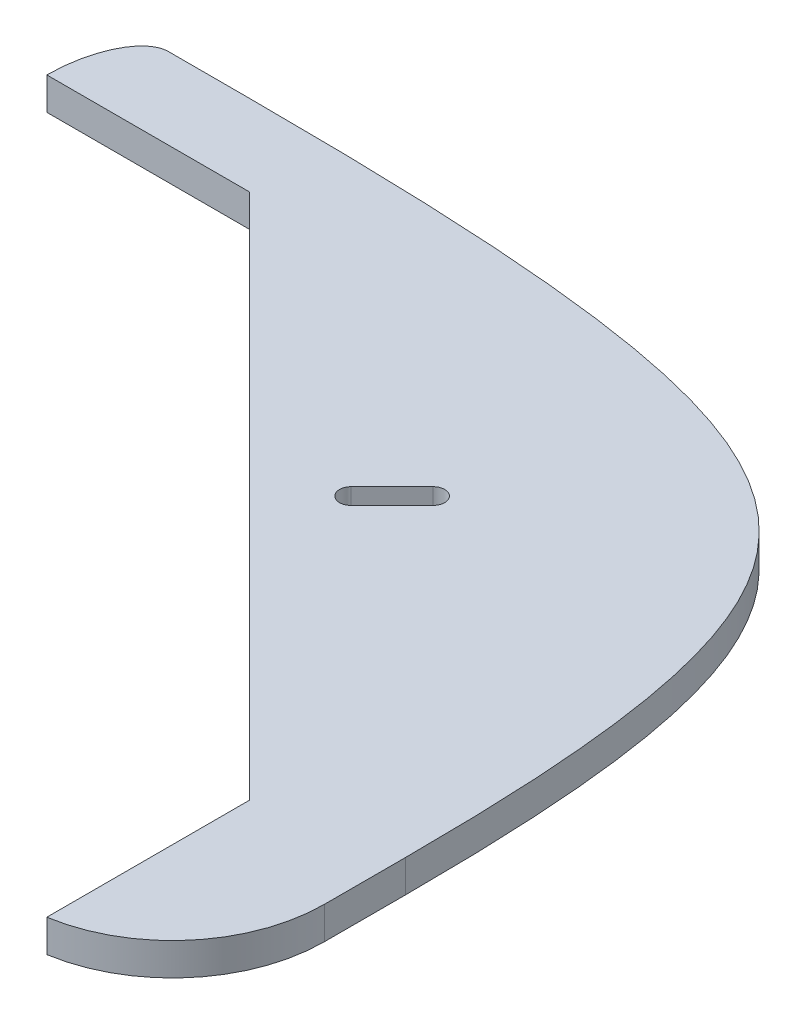
SolidWorks part; units mm, degrees
ref_plane "Front Plane" through (0, 0, 0) normal (0, 0, 1) x (1, 0, 0)
ref_plane "Top Plane" through (0, 0, 0) normal (0, 1, 0) x (1, 0, 0)
ref_plane "Right Plane" through (0, 0, 0) normal (1, 0, 0) x (0, 0, -1)
sketch "Sketch1" plane through (0, 0, 0) normal (0, 1, 0) x (1, 0, 0)
  line L1 (0, 120.65) -> (12.7, 120.65)
  line L3 (120.65, 0) -> (120.65, 12.7)
  line L4 (0, 107.95) -> (25.4, 107.95)
  line L5 (25.4, 107.95) -> (107.95, 25.4)
  line L6 (107.95, 25.4) -> (107.95, 0)
  line L7 (0, 0) -> (0, 107.95) construction
  line L8 (0, 107.95) -> (0, 120.65)
  line L9 (0, 0) -> (107.95, 0) construction
  line L10 (107.95, 0) -> (120.65, 0)
  line L12 (74.6363, 74.6363) -> (66.675, 66.675) construction
  line L13 (74.6363, 74.6363) -> (81.0709, 81.0709) construction
  line L14 (73.3635, 75.909) -> (79.7981, 82.3437)
  line L15 (75.909, 73.3635) -> (82.3437, 79.7981)
  line L16 (81.0709, 81.0709) -> (89.0322, 89.0322) construction
  arc A0 (12.7, 120.65) -> (120.65, 12.7) centre (12.7, 12.7) cw
  arc A1 (73.3635, 75.909) -> (75.909, 73.3635) centre (74.6363, 74.6363) ccw
  arc A2 (82.3437, 79.7981) -> (79.7981, 82.3437) centre (81.0709, 81.0709) ccw
  point P15 (77.8536, 77.8536)
  point P20 (73.3635, 73.3635)
  point P21 (82.3437, 82.3437)
  point P23 (79.1264, 76.5808)
  dimension "D5" = 12.7
  dimension "D1" = 25.4
  dimension "D2" = 120.65
  dimension "D3" = 12.7
  dimension "D4" = 12.7
  dimension "D6" = 3.6
extrude "Boss-Extrude1" add sketch "Sketch1" along normal blind 5.08
sketch "Sketch2" plane through (0, 0, 0) normal (-1, 0, 0) x (0, 0, 1)
  line L4 (-120.65, 0) -> (-107.95, 0)
  line L5 (-107.95, 0) -> (-107.95, 5.08)
  line L6 (-107.95, 5.08) -> (-120.65, 5.08)
  line L7 (-120.65, 5.08) -> (-120.65, 0)
  line L8 (-120.65, 0) -> (-107.95, 0)
  line L9 (-107.95, 0) -> (-107.95, 5.08)
  line L10 (-107.95, 5.08) -> (-120.65, 5.08)
  line L11 (-120.65, 5.08) -> (-120.65, 0)
  dimension "D1" = 0
extrude "Boss-Extrude2" add sketch "Sketch2" along normal blind 6.35
fillet "Fillet3" radius 6.35 1 edges at (-6.35, 2.54, -120.65) second distance 12.7 first distance on face at (3.175, 2.54, -120.65)
sketch "Sketch3" plane through (0, 5.08, 0) normal (0, 1, 0) x (1, 0, 0)
  line L0 (107.95, 0) -> (107.95, -6.35)
  line L1 (127.95, 17.1593) -> (127.95, 29.8593)
  line L5 (12.7, 120.65) -> (0, 120.65) construction
  line L6 (107.95, 25.4) -> (107.95, 104.8946) construction
  line L7 (107.95, 25.4) -> (107.95, 0) construction
  line L13 (12.7, 120.65) -> (0, 120.65)
  line L14 (-6.35, 107.95) -> (25.4, 107.95)
  line L15 (25.4, 107.95) -> (107.95, 25.4)
  line L16 (107.95, 25.4) -> (107.95, 0)
  line L17 (107.95, 0) -> (120.65, 0)
  line L18 (120.65, 0) -> (120.65, 12.7)
  line L24 (120.65, 0) -> (120.65, 12.7)
  line L25 (107.95, 0) -> (120.65, 0)
  arc A0 (127.95, 17.1593) -> (107.95, -6.35) centre (104.1329, 17.1593) cw
  arc A3 (120.65, 12.7) -> (12.7, 120.65) centre (12.7, 12.7) ccw
  arc A4 (120.65, 12.7) -> (12.7, 120.65) centre (12.7, 12.7) ccw
  conic Q0 (127.95, 29.8593) -> (12.7, 120.65) control (127.95, 120.65) rho 0.652928
  spline S1 degree 2 poles (151.9379, -867.7392) (37.4087, 143.7852) (-1.8345, 120.1085) (-2.5931, 119.6508) (-3.2729, 118.8331) (-4.3609, 117.5245) (-5.114, 115.4784) (-5.7397, 113.7784) (-6.0569, 111.7637) (-22.363, 8.1938) (868.5713, -376.3138) knots -5.340282 -5.340282 -5.340282 0.125 0.125 0.25 0.25 0.5 0.5 0.75 0.75 14.65957 14.65957 14.65957 only from (0, 120.65) to (-6.35, 107.95)
  dimension "D1" = 20
  dimension "D2" = 6.35
  dimension "D3" = 12.7
  dimension "D4" = 0
extrude "Boss-Extrude3" add sketch "Sketch3" against normal up to surface (5.08 mm away)
equation "\"Foamcore\"= 0.2in"
equation "\"MDF\"= 0.2in"
equation "\"D1@Boss-Extrude1\"=\"MDF\""
